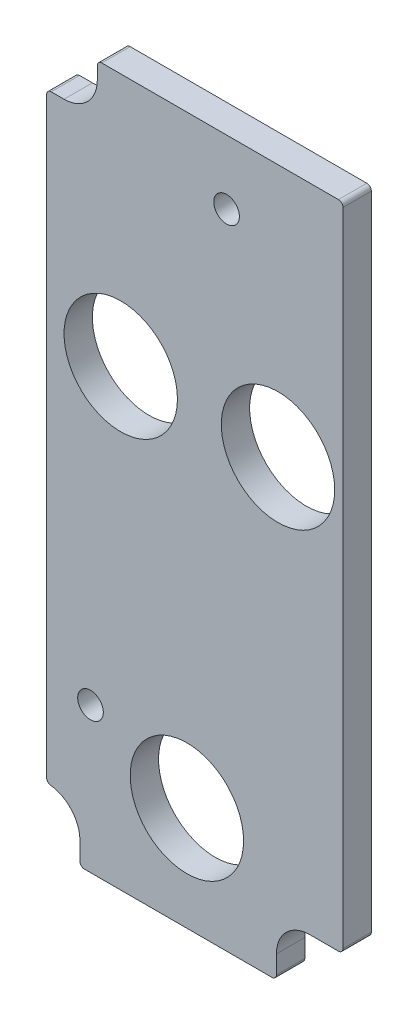
SolidWorks part; units mm, degrees
material "Acrylic (Medium-high impact)"
ref_plane "Front Plane" through (0, 0, 0) normal (0, 0, 1) x (1, 0, 0)
ref_plane "Top Plane" through (0, 0, 0) normal (0, 1, 0) x (1, 0, 0)
ref_plane "Right Plane" through (0, 0, 0) normal (1, 0, 0) x (0, 0, -1)
sketch "Sketch1" plane through (0, 0, 0) normal (0, 0, 1) x (1, 0, 0)
  line L9 (-0.762, 22.86) -> (-0.762, 130.683)
  line L10 (-1.524, 131.445) -> (-41.275, 131.445)
  line L11 (-42.037, 130.683) -> (-42.037, 128.5875)
  line L12 (-47.625, 122.9995) -> (-49.784, 122.9995)
  line L13 (-50.546, 122.2375) -> (-50.546, 22.8141)
  line L14 (-44.958, 16.51) -> (-44.958, 13.462)
  line L15 (-44.196, 12.7) -> (-12.7, 12.7)
  line L16 (-11.938, 13.462) -> (-11.938, 16.51)
  line L17 (-6.35, 22.098) -> (-1.524, 22.098)
  line L18 (-0.762, 22.86) -> (-0.762, 130.683)
  line L19 (-1.524, 131.445) -> (-41.275, 131.445)
  line L20 (-42.037, 130.683) -> (-42.037, 128.5875)
  line L21 (-47.625, 122.9995) -> (-49.784, 122.9995)
  line L22 (-50.546, 122.2375) -> (-50.546, 22.8141)
  line L23 (-44.958, 16.51) -> (-44.958, 13.462)
  line L24 (-44.196, 12.7) -> (-12.7, 12.7)
  line L25 (-11.938, 13.462) -> (-11.938, 16.51)
  line L26 (-6.35, 22.098) -> (-1.524, 22.098)
  arc A10 (-1.524, 22.098) -> (-0.762, 22.86) centre (-1.524, 22.86) ccw
  arc A11 (-0.762, 130.683) -> (-1.524, 131.445) centre (-1.524, 130.683) ccw
  arc A12 (-41.275, 131.445) -> (-42.037, 130.683) centre (-41.275, 130.683) ccw
  arc A13 (-47.625, 122.9995) -> (-42.037, 128.5875) centre (-47.625, 128.5875) ccw
  arc A14 (-49.784, 122.9995) -> (-50.546, 122.2375) centre (-49.784, 122.2375) ccw
  arc A15 (-50.546, 22.8141) -> (-49.8754, 22.0576) centre (-49.784, 22.8141) ccw
  arc A16 (-44.958, 16.51) -> (-49.8754, 22.0576) centre (-50.546, 16.51) ccw
  arc A17 (-44.958, 13.462) -> (-44.196, 12.7) centre (-44.196, 13.462) ccw
  arc A18 (-12.7, 12.7) -> (-11.938, 13.462) centre (-12.7, 13.462) ccw
  arc A19 (-6.35, 22.098) -> (-11.938, 16.51) centre (-6.35, 16.51) ccw
  arc A20 (-1.524, 22.098) -> (-0.762, 22.86) centre (-1.524, 22.86) ccw
  arc A21 (-0.762, 130.683) -> (-1.524, 131.445) centre (-1.524, 130.683) ccw
  arc A22 (-41.275, 131.445) -> (-42.037, 130.683) centre (-41.275, 130.683) ccw
  arc A23 (-47.625, 122.9995) -> (-42.037, 128.5875) centre (-47.625, 128.5875) ccw
  arc A24 (-49.784, 122.9995) -> (-50.546, 122.2375) centre (-49.784, 122.2375) ccw
  arc A25 (-50.546, 22.8141) -> (-49.8754, 22.0576) centre (-49.784, 22.8141) ccw
  arc A26 (-44.958, 16.51) -> (-49.8754, 22.0576) centre (-50.546, 16.51) ccw
  arc A27 (-44.958, 13.462) -> (-44.196, 12.7) centre (-44.196, 13.462) ccw
  arc A28 (-12.7, 12.7) -> (-11.938, 13.462) centre (-12.7, 13.462) ccw
  arc A29 (-6.35, 22.098) -> (-11.938, 16.51) centre (-6.35, 16.51) ccw
  dimension "D1" = 0
extrude "Boss-Extrude1" add sketch "Sketch1" along normal blind 4.7625
hole_wizard "3/4 (0.75) Diameter Hole1" positions "Sketch3" profile "Sketch2" hole size "3/4" standard "ANSI Inch" end condition through all
sketch "Sketch3" plane through (0, 0, 4.7625) normal (0, 0, 1) x (1, 0, 0)
  point P0 (-38.1, 88.9)
  point P3 (-11.684, 88.9)
  point P6 (-26.9875, 30.1625)
sketch "Sketch2" plane through (-38.1, 88.9, 4.7625) normal (1, 0, 0) x (0, -1, 0)
  line L0 (0, 0) -> (0, 4.7625)
  line L1 (0, 4.7625) -> (9.525, 4.7625)
  line L2 (9.525, 4.7625) -> (9.525, 0)
  line L5 (9.525, 0) -> (0, 0)
  line L11 (0, -6.35) -> (0, 107.95) construction
  dimension "Thru Hole Dia." = 19.05
  dimension "Thru Hole Depth" = 4.7625
hole_wizard "#6 Clearance Hole1" positions "Sketch5" profile "Sketch4" hole size "#6" standard "ANSI Inch" end condition through all
sketch "Sketch5" plane through (0, 0, 4.7625) normal (0, 0, 1) x (1, 0, 0)
  point P0 (-20.32, 120.65)
  point P3 (-43.18, 37.084)
sketch "Sketch4" plane through (-20.32, 120.65, 4.7625) normal (1, 0, 0) x (0, -1, 0)
  line L0 (0, 0) -> (0, 4.7625)
  line L1 (0, 4.7625) -> (2.1526, 4.7625)
  line L2 (2.1526, 4.7625) -> (2.1526, 0)
  line L5 (2.1526, 0) -> (0, 0)
  line L11 (0, -6.35) -> (0, 107.95) construction
  dimension "Thru Hole Dia." = 4.3053
  dimension "Thru Hole Depth" = 4.7625
